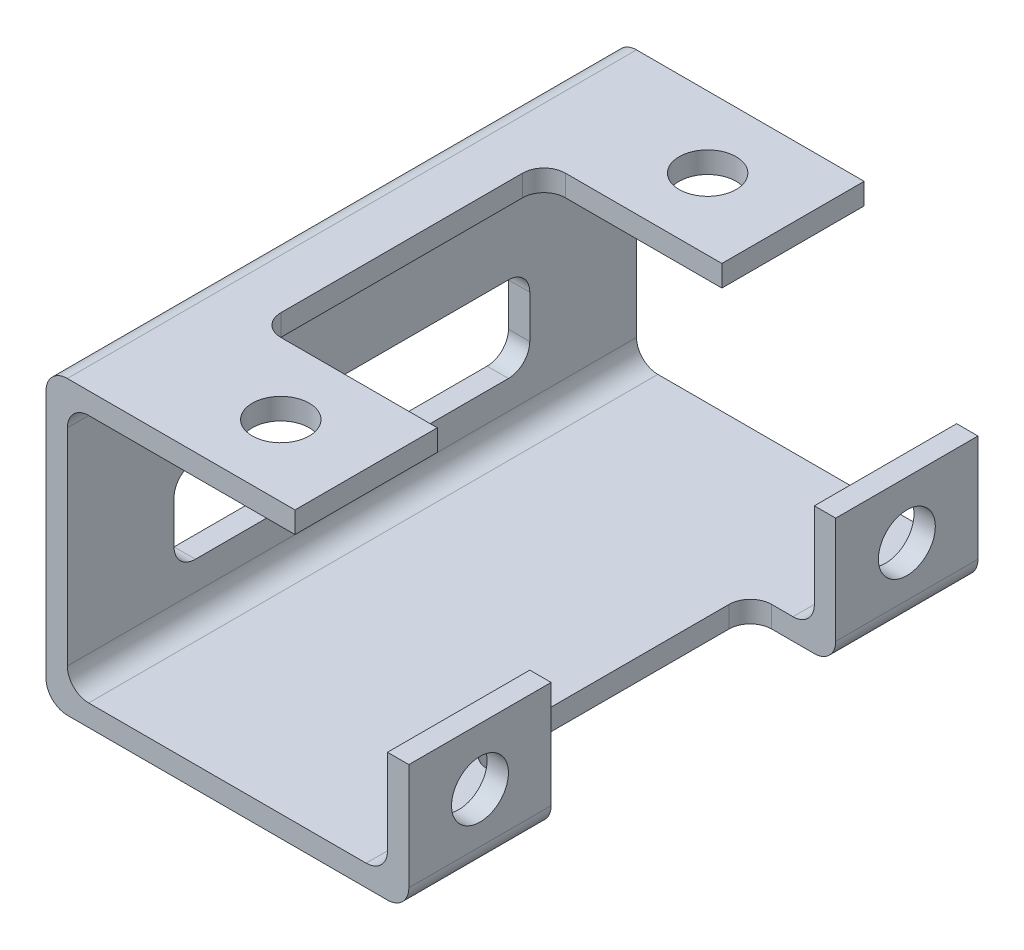
SolidWorks part; units mm, degrees
ref_plane "Front Plane" through (0, 0, 0) normal (0, 0, 1) x (1, 0, 0)
ref_plane "Top Plane" through (0, 0, 0) normal (0, 1, 0) x (1, 0, 0)
ref_plane "Right Plane" through (0, 0, 0) normal (1, 0, 0) x (0, 0, -1)
sketch "Sketch2" plane through (0, 0, 0) normal (0, 1, 0) x (1, 0, 0)
  line L1 (0, 0) -> (45, 0)
  line L2 (0, 0) -> (0, -80)
  line L3 (0, -80) -> (45, -80)
  line L4 (45, 0) -> (45, -80)
  dimension "D1" = 80
  dimension "D2" = 45
extrude "Boss-Extrude2" add sketch "Sketch2" along normal blind 35
shell "Shell2" thickness 3 removed face at (22.5, 17.5, 80) removed face at (22.5, 17.5, 0) outward yes
sketch "Sketch5" plane through (0, 38, 0) normal (0, 1, 0) x (1, 0, 0)
  line L0 (32, 0) -> (32, -20)
  line L1 (48, 0) -> (-3, 0) construction
  line L2 (32, -20) -> (7, -20)
  line L3 (7, -20) -> (7, -60)
  line L4 (7, -60) -> (32, -60)
  line L5 (32, -60) -> (32, -80)
  line L6 (-3, -80) -> (48, -80) construction
  line L10 (-3, -40) -> (48, -40) construction
  line L11 (48, -80) -> (48, 0) construction
  line L12 (32, 0) -> (48, 0)
  line L13 (48, 0) -> (48, -80)
  line L14 (48, -80) -> (32, -80)
  line L15 (-3, 0) -> (-3, -80) construction
  circle A0 centre (20, -70) radius 4
  circle A1 centre (20, -10) radius 4
  point P22 (0, 0)
  dimension "D1" = 8
  dimension "D2" = 8
  dimension "D4" = 25
  dimension "D5" = 12
  dimension "D8" = 40
  dimension "D3" = 35
  dimension "D6" = 10
  dimension "D7" = 10
extrude "Cut-Extrude1" cut sketch "Sketch5" against normal up to surface (3 mm away) contours A0 | A1 | L0 L2 L3 L4 L5 L14 L13 L12 up to face at (22.5, 35, 40)
sketch "Sketch6" plane through (48, 0, 0) normal (1, 0, 0) x (0, 0, -1)
  line L0 (-80, 15) -> (-60, 15)
  line L1 (-80, 35) -> (-80, -3) construction
  line L2 (-60, 15) -> (-60, -3)
  line L3 (-80, -3) -> (0, -3) construction
  line L4 (-60, -3) -> (-20, -3)
  line L5 (-20, -3) -> (-20, 15)
  line L6 (-20, 15) -> (0, 15)
  line L7 (0, 35) -> (0, -3) construction
  line L8 (0, 15) -> (0, 35)
  line L9 (0, 35) -> (-80, 35)
  line L10 (-80, 35) -> (-80, 15)
  line L11 (-40, 35) -> (-40, -3) construction
  circle A0 centre (-70, 7) radius 4
  circle A1 centre (-10, 7) radius 4
  point P22 (-40, 35)
  point P23 (0, 0)
  dimension "D1" = 8
  dimension "D2" = 8
  dimension "D3" = 10
  dimension "D4" = 10
  dimension "D5" = 8
  dimension "D6" = 8
  dimension "D7" = 40
  dimension "D8" = 18
extrude "Cut-Extrude2" cut sketch "Sketch6" against normal up to surface (3 mm away) up to face at (45, 17.5, 40)
sketch "Sketch7" plane through (0, -3, 0) normal (0, -1, 0) x (1, 0, 0)
  line L1 (48, 60) -> (36, 60)
  line L2 (48, 60) -> (48, 20)
  line L3 (48, 20) -> (36, 20)
  line L4 (36, 60) -> (36, 20)
  dimension "D1" = 12
  dimension "D2" = 40
extrude "Cut-Extrude3" cut sketch "Sketch7" against normal up to surface (3 mm away) up to face at (30, 0, 40)
sketch "Sketch8" plane through (-3, 0, 0) normal (-1, 0, 0) x (0, 0, 1)
  line L0 (40, -3) -> (40, 38) construction
  line L1 (15, 19) -> (65, 19)
  line L2 (15, 19) -> (15, 7)
  line L3 (15, 7) -> (65, 7)
  line L4 (65, 19) -> (65, 7)
  line L5 (0, -3) -> (80, -3) construction
  line L6 (0, 38) -> (80, 38) construction
  dimension "D1" = 12
  dimension "D2" = 50
  dimension "D3" = 10
extrude "Cut-Extrude4" cut sketch "Sketch8" against normal up to surface (3 mm away) up to face at (0, 17.5, 40)
fillet "Fillet1" radius 3 12 edges at (0, 35, 40) (45, 0, 10) (45, 0, 70) (7, 36.5, 60) (7, 36.5, 20) (-3, 38, 40) (-3, -3, 40) (36, -1.5, 60) (36, -1.5, 20) (48, -3, 10) (48, -3, 70) (0, 0, 40)
fillet "Fillet2" radius 3 4 edges at (-1.5, 19, 15) (-1.5, 19, 65) (-1.5, 7, 65) (-1.5, 7, 15)
equation "\"Length\"=80"
equation "\"D1@Sketch2\"=\"Length\""
equation "\"Width\"=45"
equation "\"D2@Sketch2\"=\"Width\""
equation "\"Height\"=35"
equation "\"D1@Boss-Extrude2\"=\"Height\""
equation "\"D8@Sketch5\"=\"Length\"/2"
